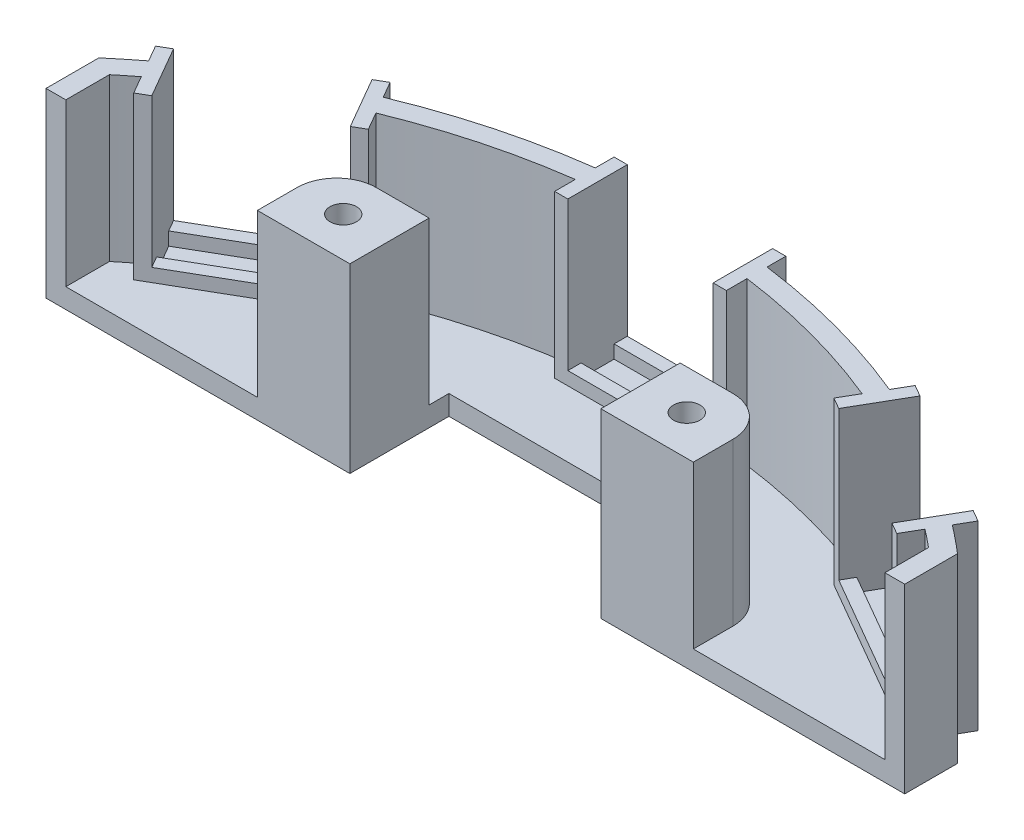
SolidWorks part; units mm, degrees
ref_plane "前视基准面" through (0, 0, 0) normal (0, 0, 1) x (1, 0, 0)
ref_plane "上视基准面" through (0, 0, 0) normal (0, 1, 0) x (1, 0, 0)
ref_plane "右视基准面" through (0, 0, 0) normal (1, 0, 0) x (0, 0, -1)
sketch "草图1" plane through (0, 0, 0) normal (0, 1, 0) x (1, 0, 0)
  line L0 (-100, 0) -> (100, 0)
  line L1 (0, 0) -> (0, 97.5)
  line L2 (19, 17) -> (-19, 17)
  line L3 (19, 17) -> (19, 83)
  line L4 (19, 83) -> (-19, 83)
  line L5 (-19, 17) -> (-19, 83)
  line L6 (19, 17) -> (-19, 83) construction
  line L7 (19, 83) -> (-19, 17) construction
  line L8 (0, 0) -> (48.75, 84.4375)
  line L9 (0, 0) -> (-48.75, 84.4375)
  line L10 (-150.1814, 68) -> (135.9874, 68)
  line L11 (-62.2583, 81.8346) -> (-39.7417, 94.8346)
  line L12 (-62.2583, 81.8346) -> (-57.7583, 74.0404)
  line L13 (-57.7583, 74.0404) -> (-35.2417, 87.0404)
  line L14 (-39.7417, 94.8346) -> (-35.2417, 87.0404)
  line L15 (-62.2583, 81.8346) -> (-35.2417, 87.0404) construction
  line L16 (-57.7583, 74.0404) -> (-39.7417, 94.8346) construction
  line L17 (-13, 102) -> (13, 102)
  line L18 (-13, 102) -> (-13, 93)
  line L19 (-13, 93) -> (13, 93)
  line L20 (13, 102) -> (13, 93)
  line L21 (-13, 102) -> (13, 93) construction
  line L22 (-13, 93) -> (13, 102) construction
  line L23 (39.7417, 94.8346) -> (62.2583, 81.8346)
  line L24 (39.7417, 94.8346) -> (35.2417, 87.0404)
  line L25 (35.2417, 87.0404) -> (57.7583, 74.0404)
  line L26 (62.2583, 81.8346) -> (57.7583, 74.0404)
  line L27 (39.7417, 94.8346) -> (57.7583, 74.0404) construction
  line L28 (35.2417, 87.0404) -> (62.2583, 81.8346) construction
  line L29 (-65, 114.503) -> (-65, -14.8084)
  line L30 (65, 110.1512) -> (65, -26.6205)
  circle A0 centre (0, 0) radius 100
  point P5 (0, 50)
  dimension "D1" = 200
  dimension "D2" = 50
  dimension "D3" = 66
  dimension "D4" = 38
  dimension "D5" = 97.5
  dimension "D6" = 97.5
  dimension "D7" = 97.5
  dimension "D8" = 30
  dimension "D9" = 30
  dimension "D10" = 9
  dimension "D11" = 26
  dimension "D12" = 26
  dimension "D13" = 9
  dimension "D14" = 9
  dimension "D15" = 26
  dimension "D16" = 68
  dimension "D17" = 65
  dimension "D18" = 65
extrude "底座" add sketch "草图1" against normal blind 3 contours L12 A0 L29 L10 L9 L13 | L18 A0 L14 L13 L9 L10 L5 L4 L1 L19 | L24 A0 L20 L19 L1 L4 L3 L10 L8 L25 | L30 A0 L26 L25 L8 L10 | L13 L14 L11 L12 | L24 L25 L26 L23 | L18 L19 L20 L17 region at (-53.0217, 0, -72.6681) region at (-24.5296, 0, -83.3703) region at (53.0217, 0, -72.6681) region at (24.5296, 0, -83.3703)
sketch "草图5" plane through (0, 0, 0) normal (0, 1, 0) x (1, 0, 0)
  line L0 (0, 0) -> (0, 97.5)
  line L1 (0, 0) -> (48.75, 84.4375)
  line L2 (0, 0) -> (-48.75, 84.4375)
  line L4 (-62.2583, 81.8346) -> (-39.7417, 94.8346)
  line L5 (-62.2583, 81.8346) -> (-57.7583, 74.0404)
  line L6 (-57.7583, 74.0404) -> (-35.2417, 87.0404)
  line L7 (-39.7417, 94.8346) -> (-35.2417, 87.0404)
  line L8 (-62.2583, 81.8346) -> (-35.2417, 87.0404) construction
  line L9 (-57.7583, 74.0404) -> (-39.7417, 94.8346) construction
  line L10 (-13, 102) -> (13, 102)
  line L11 (-13, 102) -> (-13, 93)
  line L12 (-13, 93) -> (13, 93)
  line L13 (13, 102) -> (13, 93)
  line L14 (-13, 102) -> (13, 93) construction
  line L15 (-13, 93) -> (13, 102) construction
  line L16 (39.7417, 94.8346) -> (62.2583, 81.8346)
  line L17 (39.7417, 94.8346) -> (35.2417, 87.0404)
  line L18 (35.2417, 87.0404) -> (57.7583, 74.0404)
  line L19 (62.2583, 81.8346) -> (57.7583, 74.0404)
  line L20 (39.7417, 94.8346) -> (57.7583, 74.0404) construction
  line L21 (35.2417, 87.0404) -> (62.2583, 81.8346) construction
  line L33 (-62, 27.521) -> (-62, 157.7235)
  line L34 (62, 18.3586) -> (62, 161.5814)
  line L35 (65, 75.9934) -> (65, 68) construction
  line L36 (-65, 75.9934) -> (-65, 68) construction
  line L38 (-19, 68) -> (-33, 68)
  line L39 (-19, 68) -> (-19, 80)
  line L40 (-19, 80) -> (-33, 80)
  line L41 (-33, 68) -> (-33, 80)
  line L42 (19, 68) -> (33, 68)
  line L43 (19, 68) -> (19, 80)
  line L44 (19, 80) -> (33, 80)
  line L45 (33, 68) -> (33, 80)
  circle A24 centre (0, 0) radius 97
  arc M10 (65, 75.9934) -> (60.834, 79.3676) centre (0, 0) ccw
  arc M14 (38.3174, 92.3676) -> (13, 99.1514) centre (0, 0) ccw
  arc M18 (-13, 99.1514) -> (-38.3174, 92.3676) centre (0, 0) ccw
  arc M22 (-60.834, 79.3676) -> (-65, 75.9934) centre (0, 0) ccw
  line M23 (-65, 75.9934) -> (-65, 68)
  line M24 (-65, 68) -> (-19, 68)
  line M25 (-19, 68) -> (-19, 83)
  line M27 (19, 83) -> (19, 68)
  line M28 (19, 68) -> (65, 68)
  line M29 (65, 68) -> (65, 75.9934)
  dimension "D14" = 194
  dimension "D1" = 30
  dimension "D2" = 30
  dimension "D3" = 97.5
  dimension "D4" = 97.5
  dimension "D5" = 97.5
  dimension "D6" = 26
  dimension "D7" = 9
  dimension "D8" = 26
  dimension "D9" = 9
  dimension "D10" = 26
  dimension "D11" = 9
  dimension "D12" = 3
  dimension "D13" = 3
  dimension "D15" = 14
  dimension "D16" = 12
  dimension "D17" = 12
  dimension "D18" = 14
extrude "侧壁" add sketch "草图5" along normal blind 24.5 contours L33 A24 M23 M24 | A24 L33 M22 M23 | A24 L5 L33 M22 | A24 L11 L7 M18 | A24 L17 L13 M14 | A24 L34 L19 M10 | A24 L34 M29 M10 | A24 L34 M29 M28 | L41 L40 M24 M25 | L45 L44 M28 M27 | L4 L7 L6 L5 | L10 L13 L12 L11 | L16 L19 L18 L17 region at (-26, 0, -74) region at (26, 0, -74) region at (63.3778, 0, -70.7116) region at (-63.3778, 0, -70.7116) region at (25.4265, 0, -94.893) region at (-25.4265, 0, -94.893) region at (60.9921, 0, -77.0857) region at (63.5084, 0, -75.2731) region at (-63.5084, 0, -75.2731) region at (-60.9921, 0, -77.0857)
sketch "草图8" plane through (0, 24.5, 0) normal (0, 1, 0) x (1, 0, 0)
  line L0 (0, 0) -> (0, 97.5)
  line L1 (0, 0) -> (48.75, 84.4375)
  line L2 (0, 0) -> (-48.75, 84.4375)
  line L4 (-36.9737, 86.0404) -> (-56.0263, 75.0404)
  line L5 (-36.9737, 86.0404) -> (-41.4737, 93.8346)
  line L6 (-41.4737, 93.8346) -> (-60.5263, 82.8346)
  line L7 (-56.0263, 75.0404) -> (-60.5263, 82.8346)
  line L8 (-36.9737, 86.0404) -> (-60.5263, 82.8346) construction
  line L9 (-41.4737, 93.8346) -> (-56.0263, 75.0404) construction
  line L10 (-11, 93) -> (11, 93)
  line L11 (-11, 93) -> (-11, 102)
  line L12 (-11, 102) -> (11, 102)
  line L13 (11, 93) -> (11, 102)
  line L14 (-11, 93) -> (11, 102) construction
  line L15 (-11, 102) -> (11, 93) construction
  line L16 (36.9737, 86.0404) -> (56.0263, 75.0404)
  line L17 (36.9737, 86.0404) -> (41.4737, 93.8346)
  line L18 (41.4737, 93.8346) -> (60.5263, 82.8346)
  line L19 (56.0263, 75.0404) -> (60.5263, 82.8346)
  line L20 (36.9737, 86.0404) -> (60.5263, 82.8346) construction
  line L21 (41.4737, 93.8346) -> (56.0263, 75.0404) construction
  dimension "D1" = 30
  dimension "D2" = 30
  dimension "D3" = 97.5
  dimension "D4" = 97.5
  dimension "D5" = 97.5
  dimension "D6" = 22
  dimension "D7" = 22
  dimension "D8" = 22
  dimension "D9" = 9
  dimension "D10" = 9
  dimension "D11" = 9
extrude "开口" cut sketch "草图8" against normal blind 22.5 contours L6 L7 L4 L5 | L12 L13 L10 L11 | L18 L19 L16 L17
sketch "草图9" plane through (0, 2, 0) normal (0, 1, 0) x (1, 0, 0)
  line L0 (0, 0) -> (0, 97.5)
  line L1 (0, 0) -> (-48.75, 84.4375)
  line L2 (0, 0) -> (48.75, 84.4375)
  line L4 (-59.5263, 81.1025) -> (-40.4737, 92.1025)
  line L5 (-59.5263, 81.1025) -> (-57.0263, 76.7724)
  line L6 (-57.0263, 76.7724) -> (-37.9737, 87.7724)
  line L7 (-40.4737, 92.1025) -> (-37.9737, 87.7724)
  line L8 (-59.5263, 81.1025) -> (-37.9737, 87.7724) construction
  line L9 (-57.0263, 76.7724) -> (-40.4737, 92.1025) construction
  line L10 (-11, 100) -> (11, 100)
  line L11 (-11, 100) -> (-11, 95)
  line L12 (-11, 95) -> (11, 95)
  line L13 (11, 100) -> (11, 95)
  line L14 (-11, 100) -> (11, 95) construction
  line L15 (-11, 95) -> (11, 100) construction
  line L16 (40.4737, 92.1025) -> (59.5263, 81.1025)
  line L17 (40.4737, 92.1025) -> (37.9737, 87.7724)
  line L18 (37.9737, 87.7724) -> (57.0263, 76.7724)
  line L19 (59.5263, 81.1025) -> (57.0263, 76.7724)
  line L20 (40.4737, 92.1025) -> (57.0263, 76.7724) construction
  line L21 (37.9737, 87.7724) -> (59.5263, 81.1025) construction
  dimension "D1" = 30
  dimension "D2" = 30
  dimension "D3" = 97.5
  dimension "D4" = 97.5
  dimension "D5" = 97.5
  dimension "D6" = 22
  dimension "D7" = 5
  dimension "D8" = 5
  dimension "D9" = 22
  dimension "D10" = 22
  dimension "D11" = 5
extrude "卡槽" cut sketch "草图9" against normal blind 2 contours L7 L6 L5 L4 | L10 L13 L12 L11 | L16 L19 L18 L17
sketch "草图6" plane through (0, -3, 0) normal (0, -1, 0) x (1, 0, 0)
  circle A0 centre (-26, -74) radius 2
  circle A1 centre (26, -74) radius 2
  point P7 (0, 0)
  point P8 (-22.3904, -62.6816)
  point P11 (-12.1567, -28.8505)
  dimension "D1" = 4
  dimension "D2" = 4
  dimension "D3" = 74
  dimension "D4" = 74
  dimension "D5" = 26
  dimension "D6" = 26
extrude "螺丝孔" cut sketch "草图6" against normal through all
fillet "圆角2" radius 6 2 edges at (-33, 12.25, -80) (33, 12.25, -80)
